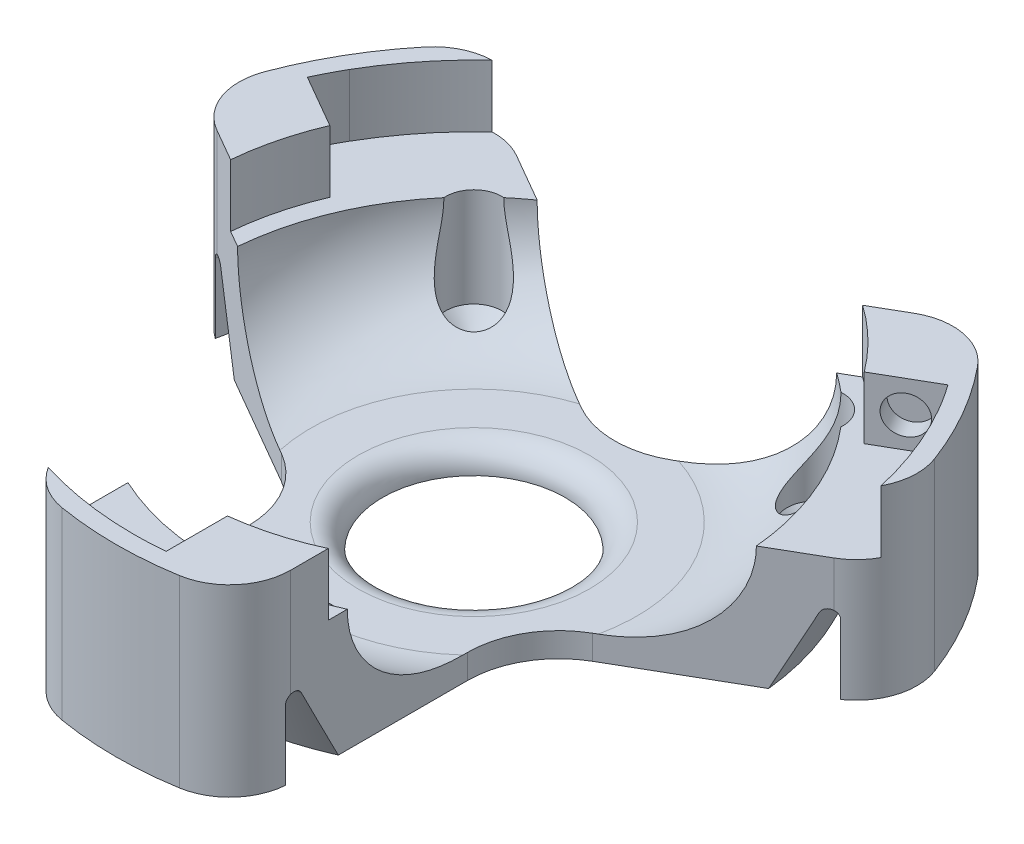
SolidWorks part; units mm, degrees
ref_plane "Front Plane" through (0, 0, 0) normal (0, 0, 1) x (1, 0, 0)
ref_plane "Top Plane" through (0, 0, 0) normal (0, 1, 0) x (1, 0, 0)
ref_plane "Right Plane" through (0, 0, 0) normal (1, 0, 0) x (0, 0, -1)
sketch "Sketch1" plane through (0, 0, 0) normal (0, 1, 0) x (1, 0, 0)
  line L0 (-56, 0) -> (-56, 28)
  line L1 (-28, 0) -> (-28, 28)
  line L3 (-28, 0) -> (-28, 28)
  line L4 (28, 0) -> (28, 28)
  line L5 (28, 0) -> (28, 28)
  line L7 (56, 0) -> (56, 28)
  line L8 (0, 0) -> (0, 28)
  line L9 (56, 0) -> (56, 28)
  line L10 (-56, 28) -> (-56, 56)
  line L11 (-56, 56) -> (-28, 56)
  line L12 (-28, 28) -> (-28, 56)
  line L13 (-28, 28) -> (-28, 56)
  line L15 (0, 56) -> (28, 56)
  line L16 (28, 28) -> (28, 56)
  line L17 (28, 28) -> (28, 56)
  line L18 (28, 56) -> (56, 56)
  line L19 (56, 28) -> (56, 56)
  line L20 (-28, 56) -> (0, 56)
  line L21 (56, 28) -> (56, 56)
  line L23 (0, 28) -> (0, 56)
  line L24 (-56, -28) -> (-56, 0)
  line L25 (-28, -28) -> (-28, 0)
  line L27 (-28, -28) -> (-28, 0)
  line L28 (28, -28) -> (28, 0)
  line L29 (28, -28) -> (28, 0)
  line L31 (56, -28) -> (56, 0)
  line L32 (0, -28) -> (0, 0)
  line L33 (56, -28) -> (56, 0)
  line L34 (-56, 0) -> (-56, 28)
  line L35 (-56, 28) -> (-28, 28)
  line L36 (-28, 0) -> (-28, 28)
  line L37 (-28, 0) -> (-28, 28)
  line L38 (0, 0) -> (0, 28)
  line L39 (0, 28) -> (28, 28)
  line L40 (28, 0) -> (28, 28)
  line L41 (28, 0) -> (28, 28)
  line L42 (28, 28) -> (56, 28)
  line L43 (56, 0) -> (56, 28)
  line L44 (-28, 28) -> (0, 28)
  line L45 (56, 0) -> (56, 28)
  line L46 (0, 0) -> (0, 28)
  line L47 (0, 0) -> (0, 28)
  line L48 (28, -56) -> (56, -56)
  line L49 (0, -56) -> (28, -56)
  line L51 (0, -28) -> (28, -28)
  line L52 (28, -56) -> (28, -28)
  line L53 (28, -56) -> (28, -28)
  line L54 (-28, -56) -> (0, -56)
  line L55 (56, -56) -> (56, -28)
  line L56 (-56, -56) -> (-28, -56)
  line L57 (56, -56) -> (56, -28)
  line L58 (-56, -56) -> (-56, -28)
  line L59 (-56, -28) -> (-28, -28)
  line L60 (28, -28) -> (56, -28)
  line L61 (0, -28) -> (28, -28)
  line L62 (0, -28) -> (0, 0)
  line L63 (0, 0) -> (28, 0)
  line L64 (28, -28) -> (28, 0)
  line L65 (28, -28) -> (28, 0)
  line L66 (28, 0) -> (56, 0)
  line L67 (56, -28) -> (56, 0)
  line L68 (-28, -56) -> (-28, -28)
  line L69 (56, -28) -> (56, 0)
  line L70 (-28, -56) -> (-28, -28)
  line L72 (84, 0) -> (84, 28)
  line L81 (0, -56) -> (0, -28)
  line L82 (-28, -28) -> (0, -28)
  line L83 (-56, -28) -> (-28, -28)
  line L84 (-56, -28) -> (-56, 0)
  line L85 (-56, 0) -> (-28, 0)
  line L86 (-28, -28) -> (-28, 0)
  line L87 (-28, -28) -> (-28, 0)
  line L88 (-28, 0) -> (0, 0)
  line L89 (0, -28) -> (0, 0)
  line L90 (0, -28) -> (0, 0)
  line L92 (0, -56) -> (0, -28)
  line L93 (0, -28) -> (0, 0)
  line L94 (0, 0) -> (0, 28)
  line L95 (0, 28) -> (0, 56)
  dimension "D3" = 3
  dimension "D4" = 2
  dimension "D5" = 3
  dimension "D6" = 2
sketch "Sketch2" plane through (0, 0, 0) normal (0, 1, 0) x (1, 0, 0)
  circle A0 centre (0, 0) radius 42.75
  circle A1 centre (0, 0) radius 58.75
  dimension "D1" = 85.5
  dimension "D2" = 16
extrude "Boss-Extrude1" add sketch "Sketch2" along normal blind 16
sketch "Sketch4" plane through (0, 0, 0) normal (0, 0, 1) x (1, 0, 0)
  line L2 (58.75, 16) -> (-58.75, 16) construction
  line L3 (-58.75, 0) -> (58.75, 0) construction
  line L4 (42.75, 16) -> (42.75, 0)
  line L5 (42.75, 0) -> (26.75, 0)
  ellipse E0 centre (26.75, 16) end of major axis (26.75, 0) minor radius 16 (26.75, 0) -> (42.75, 16) ccw
  dimension "D1" = 16
revolve "Revolve5" add sketch "Sketch4" angle 360 about axis through (0, 16, 0) along (0, -1, 0)
sketch "Sketch5" plane through (0, 0, 0) normal (0, -1, 0) x (1, 0, 0)
  circle A0 centre (0, 0) radius 58.75
  circle A1 centre (0, 0) radius 58.75 construction
extrude "Boss-Extrude2" add sketch "Sketch5" along normal blind 4
sketch "Sketch6" plane through (0, -4, 0) normal (0, -1, 0) x (1, 0, 0)
  line L0 (18, 10.3923) -> (18, 58.2838)
  line L2 (-18, 10.3923) -> (-18, 58.2838)
  line L3 (0, -20.7846) -> (41.4752, -44.7304)
  line L4 (18, 10.3923) -> (59.4752, -13.5534)
  line L6 (0, -20.7846) -> (-41.4752, -44.7304)
  line L7 (-18, 10.3923) -> (-59.4752, -13.5534)
  arc A1 (-18, 58.2838) -> (-59.4752, -13.5534) centre (0, 0) ccw
  arc A2 (59.4752, -13.5534) -> (18, 58.2838) centre (0, 0) ccw
  arc A3 (-41.4752, -44.7304) -> (41.4752, -44.7304) centre (0, 0) ccw
  dimension "D1" = 3
extrude "Cut-Extrude1" cut sketch "Sketch6" against normal through all
sketch "Sketch9" plane through (0, 0, 0) normal (0, 1, 0) x (1, 0, 0)
  circle A0 centre (0, -28) radius 4.6
  circle A1 centre (-28, 28) radius 4.6
  circle A2 centre (28, 28) radius 4.6
  dimension "D1" = 9.2
  dimension "D2" = 9.2
  dimension "D3" = 9.2
extrude "Cut-Extrude2" cut sketch "Sketch9" along normal blind 20 and the other way blind 0.25
sketch "Sketch15" plane through (0, 0, 0) normal (0, 1, 0) x (1, 0, 0)
  circle A0 centre (0, 0) radius 15
  dimension "D1" = 30
extrude "Cut-Extrude5" cut sketch "Sketch15" against normal blind 12
fillet "Fillet1" radius 15 3 edges at (0, -2, -20.7846) (-18, -2, 10.3923) (18, -2, 10.3923)
fillet "Fillet2" radius 10 6 edges at (-18, 6, 55.9246) (-57.4321, 6, -12.3738) (-39.4321, 6, -43.5508) (39.4321, 6, -43.5508) (57.4321, 6, -12.3738) (18, 6, 55.9246)
fillet "Fillet4" radius 4 1 edges at (0, 0, 15)
hole_wizard "CSK for M4 Flat Head Machine Screw3" positions "3DSketch3" profile "Sketch14" countersink size "M4" standard "ANSI Metric" end condition through all
sketch3d "3DSketch3"
  line L0 (0, -0.25, 28) -> (0, 0, 28) construction
  line L1 (-28, -0.25, -28) -> (-28, 16, -28) construction
  line L2 (28, -0.25, -28) -> (28, 16, -28) construction
  point P0 (0, -0.25, 28)
  point P4 (-28, -0.25, -28)
  point P8 (28, -0.25, -28)
sketch "Sketch14" plane through (0, -0.25, 28) normal (1, 0, 0) x (0, 0, 1)
  line L0 (0, 0) -> (0, 3.75)
  line L1 (0, 3.75) -> (2.25, 3.75)
  line L2 (2.25, 3.75) -> (2.25, 2.45)
  line L3 (2.25, 2.45) -> (4.7, 0)
  line L5 (4.7, 0) -> (0, 0)
  line L6 (-2.25, 2.45) -> (-4.7, 0) construction
  line L11 (0, -6.35) -> (0, 107.95) construction
  dimension "Thru Hole Dia." = 4.5
  dimension "Thru Hole Depth" = 3.75
  dimension "Near C'Sink Dia." = 9.4
  dimension "Near C'Sink Angle" = 90
sketch "Sketch16" plane through (0, 16, 0) normal (0, 1, 0) x (1, 0, 0)
  line L0 (-2.5044, 1.4459) -> (-50.879, 29.375) construction
  line L1 (-50.7044, 23.3852) -> (-41.9942, 18.3564)
  line L4 (-24.5808, 34.9764) -> (-32.6464, 39.633)
  line L5 (-50.6464, 8.4561) -> (-42.5808, 3.7994)
  line L7 (-50.6464, 8.4561) -> (-45.2839, 5.3601)
  arc A0 (-45.3687, 37.3261) -> (-55.0098, 20.6274) centre (0, 0) ccw construction
  arc A1 (-41.9942, 18.3564) -> (-45.2839, 5.3601) centre (-2.5044, 1.4459) ccw
  arc A2 (-48.3675, 27.925) -> (-50.7044, 23.3852) centre (-2.5044, 1.4459) ccw
  arc A3 (-32.5881, 27.6691) -> (-42.5808, 3.7994) centre (0, 0) ccw construction
  arc A4 (-37.9586, 40.9679) -> (-48.3675, 27.925) centre (0, 0) ccw
  arc A10 (-32.6464, 39.633) -> (-45.3687, 37.3261) centre (-37.6464, 30.9728) ccw
  arc A11 (-45.3687, 37.3261) -> (-55.0098, 20.6274) centre (0, 0) ccw
  arc A12 (-55.0098, 20.6274) -> (-50.6464, 8.4561) centre (-45.6464, 17.1164) ccw
  arc A13 (-32.5881, 27.6691) -> (-42.5808, 3.7994) centre (0, 0) ccw
  arc A14 (-27.6691, 32.5881) -> (-32.5881, 27.6691) centre (-28, 28) ccw
  arc A15 (-24.5808, 34.9764) -> (-27.6691, 32.5881) centre (0, 0) ccw
  arc A16 (-37.9586, 40.9679) -> (-45.3687, 37.3261) centre (-37.6464, 30.9728) ccw
  arc A17 (-45.3687, 37.3261) -> (-55.0098, 20.6274) centre (0, 0) ccw
  arc A18 (-55.0098, 20.6274) -> (-50.6464, 8.4561) centre (-45.6464, 17.1164) ccw
  dimension "D1" = 3.1
  dimension "D2" = 13.1
  dimension "D3" = 5.1
  dimension "D4" = 0
extrude "Boss-Extrude3" add sketch "Sketch16" along normal blind 10.2
sketch "Sketch17" plane through (-2.55, 0, 4.4167) normal (0.5, 0, -0.866) x (-0.866, 0, -0.5)
  line L0 (45.5462, 26.2) -> (45.5462, 16) construction
  line L1 (45.5462, 16) -> (55.6039, 16) construction
  circle A0 centre (50.5462, 21) radius 3.1
  dimension "D1" = 6.2
  dimension "D2" = 5
  dimension "D3" = 5
extrude "Cut-Extrude6" cut sketch "Sketch17" against normal blind 3.1
pattern_circular "CirPattern1" count 3 over 360 about axis through (0, 0, 0) along (0, 1, 0) of "Boss-Extrude3", "Cut-Extrude6"
ref_plane "Plane1" through (0, 0, 0) normal (1, 0, 0) x (0, 0, -1)
sketch "Sketch18" plane through (0, 0, 0) normal (1, 0, 0) x (0, 0, -1)
  line L0 (-52.0891, -4) -> (-52.0891, 13)
  line L1 (-57.9535, -4) -> (-48.0891, -4) construction
  line L2 (-52.0891, 13) -> (-44.0891, -4)
  line L3 (-48.0891, -4) -> (-19.0526, -4) construction
  line L4 (-44.0891, -4) -> (-52.0891, -4)
  line L5 (-48.0891, 26.2) -> (-48.0891, -4) construction
  dimension "D1" = 4
  dimension "D2" = 17
  dimension "D3" = 8
revolve "Cut-Revolve1" cut sketch "Sketch18" angle 360 about axis through (0, 16, 0) along (0, -1, 0)
fillet "Fillet5" radius 1.25 3 edges at (-45.1105, 13, -26.0446) (0, 13, 52.0891) (45.1105, 13, -26.0446)
